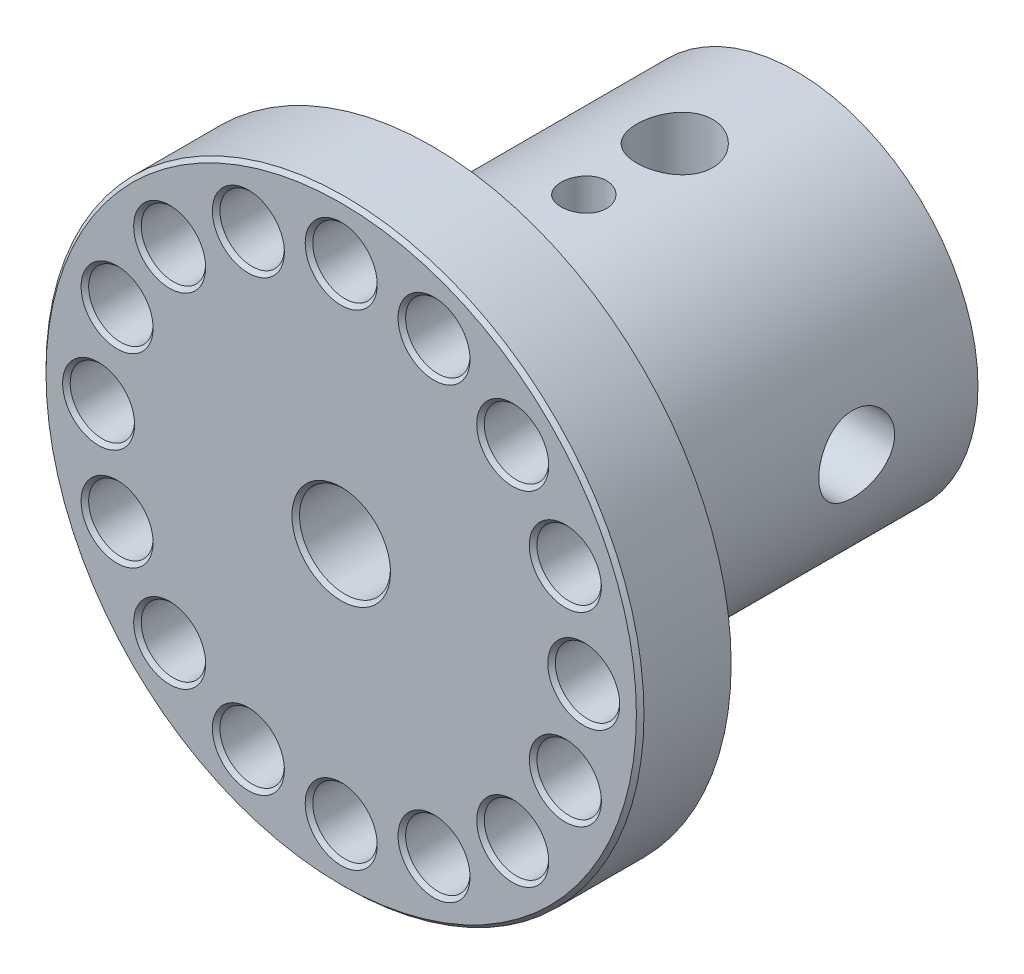
SolidWorks part; units mm, degrees
note: '?' marks a value the reader was unsure of.
ref_plane "Front" through (0, 0, 0) normal (0, 0, 1) x (1, 0, 0)
ref_plane "Top" through (0, 0, 0) normal (0, 1, 0) x (1, 0, 0)
ref_plane "Right" through (0, 0, 0) normal (1, 0, 0) x (0, 0, -1)
sketch "Sketch1" plane through (0, 0, 0) normal (1, 0, 0) x (0, 0, -1)
  line L0 (0, 31.3055) -> (0, 4.7625)
  line L1 (0, 31.3055) -> (9.525, 31.3055)
  line L2 (9.525, 31.3055) -> (9.525, 22.225)
  line L3 (12.7, 19.05) -> (47.625, 19.05)
  line L4 (47.625, 19.05) -> (47.625, 6.35)
  line L5 (47.625, 6.35) -> (25.4, 6.35)
  line L6 (25.4, 6.35) -> (25.4, 3.9687)
  line L7 (19.05, 4.7625) -> (0, 4.7625)
  line L8 (-8.5328, 0) -> (65.6828, 0) construction
  line L9 (19.05, 4.7625) -> (19.05, 3.9688)
  line L10 (19.05, 3.9688) -> (25.4, 3.9687)
  arc A0 (9.525, 22.225) -> (12.7, 19.05) centre (12.7, 22.225) ccw
  dimension "D1" = 3.175
  dimension "D2" = 9.525
  dimension "D3" = 47.625
  dimension "D4" = 9.525
  dimension "D5" = 12.7
  dimension "D6" = 38.1
  dimension "D7" = 62.611
  dimension "D8" = 22.225
  dimension "D9" = 7.9375
  dimension "D10" = 19.05
revolve "Base-Revolve" add sketch "Sketch1" angle 360 about L8
ref_axis "Axis1" through (0, 0, -41.4672) along (0, 0, 1)?
sketch "Sketch2" plane through (0, 0, 0) normal (0, 0, 1) x (1, 0, 0)
  circle A0 centre (0, 0) radius 25.4 construction
  circle A1 centre (25.4, 0) radius 3.3734
  dimension "D1" = 50.8
  dimension "D2" = 6.7469
extrude "Cut-Extrude1" cut sketch "Sketch2" against normal through all
pattern_circular "CirPattern1" count 16 every 22.5 about axis through (0, 0, 0) along (0, 0, 1) of "Cut-Extrude1"
sketch "Sketch4" plane through (0, 0, 0) normal (0, 1, 0) x (1, 0, 0)
  line L0 (0, 9.525) -> (0, 0) construction
  line L1 (3.9687, 25.4) -> (-3.9687, 25.4) construction
  circle A0 centre (0, 25.4) radius 2.3813
  dimension "D1" = 4.7625
extrude "Cut-Extrude2" cut sketch "Sketch4" along normal through all
sketch "Sketch3" plane through (0, 0, -47.625) normal (0, 0, -1) x (-1, 0, 0)
  line L0 (-1.5875, 7.9375) -> (1.5875, 7.9375)
  line L1 (-1.5875, 7.9375) -> (-1.5875, 6.1484)
  line L2 (1.5875, 7.9375) -> (1.5875, 6.1484)
  circle A0 centre (0, 0) radius 6.35 construction
  arc A1 (1.5875, 6.1484) -> (-1.5875, 6.1484) centre (0, 0) ccw
  dimension "D1" = 14.2875
  dimension "D2" = 3.175
  dimension "D3" = 1.5875
extrude "Cut-Extrude3" cut sketch "Sketch3" against normal up to next
sketch "Sketch5" plane through (0, 0, 0) normal (0, 1, 0) x (1, 0, 0)
  line L0 (0, 9.525) -> (0, 0) construction
  line L1 (19.05, 47.625) -> (-19.05, 47.625) construction
  circle A0 centre (0, 34.925) radius 3.9688
  dimension "D1" = 7.9375
  dimension "D2" = 12.7
extrude "Cut-Extrude4" cut sketch "Sketch5" along normal through all
pattern_circular "CirPattern2" count 2 every 90 about axis through (0, 0, -41.4672) along (0, 0, 1) of "Cut-Extrude4"
chamfer "Chamfer1" distance 0.3969 angle 45 18 edges at (11.0111, -26.5832, 0) (20.3459, -20.3459, 0) (4.7625, 0, 0) (31.3055, 0, 0) (26.5832, -11.0111, 0) (28.7734, 0, 0) (26.5832, 11.0111, 0) (20.3459, 20.3459, 0) (11.0111, 26.5832, 0) (0, 28.7734, 0) (-11.0111, 26.5832, 0) (-20.3459, 20.3459, 0) (-26.5832, 11.0111, 0) (-28.7734, 0, 0) (-26.5832, -11.0111, 0) (-20.3459, -20.3459, 0) (-11.0111, -26.5832, 0) (0, -28.7734, 0)
